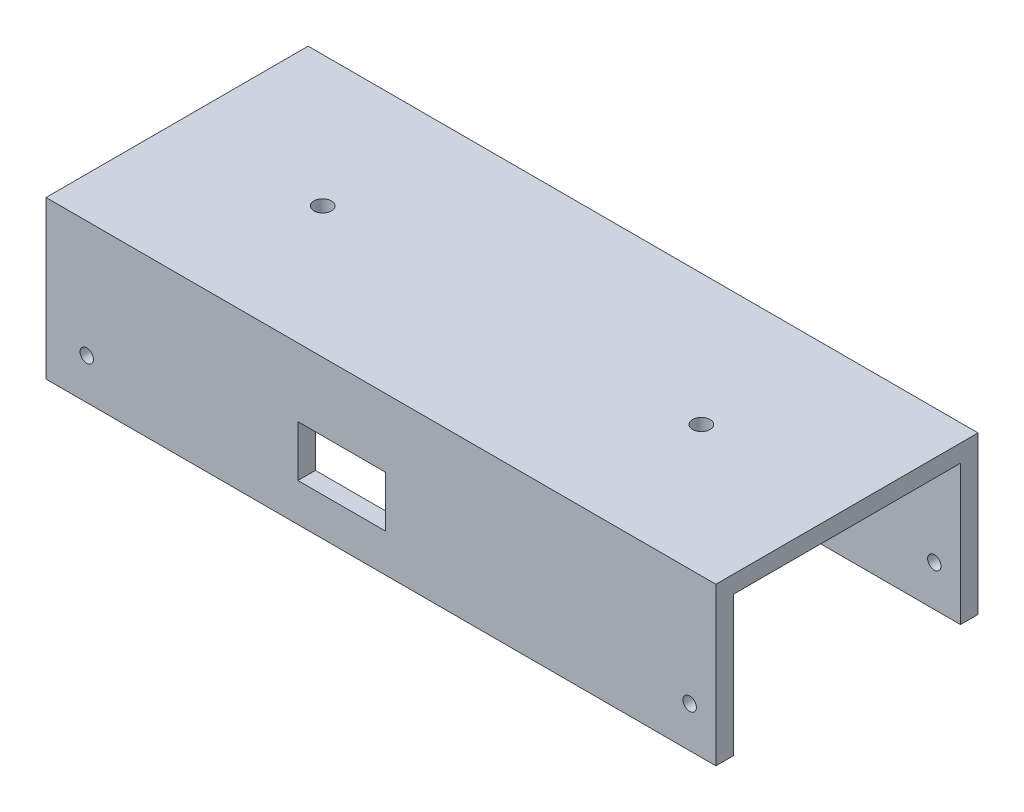
SolidWorks part; units mm, degrees
ref_plane "Front Plane" through (0, 0, 0) normal (0, 0, 1) x (1, 0, 0)
ref_plane "Top Plane" through (0, 0, 0) normal (0, 1, 0) x (1, 0, 0)
ref_plane "Right Plane" through (0, 0, 0) normal (1, 0, 0) x (0, 0, -1)
sketch "Sketch1" plane through (0, 0, 0) normal (0, 0, 1) x (1, 0, 0)
  line L9 (21.172, -17.9478) -> (91.172, -17.9478)
  line L10 (21.172, -17.9478) -> (21.172, -40.3878)
  line L11 (4.5, -8) -> (200.727, -8) construction
  line L12 (4.5, -8) -> (-67.0185, -8) construction
  line L13 (21.172, -40.3878) -> (91.172, -40.3878)
  line L14 (91.172, -17.9478) -> (91.172, -40.3878)
  line L15 (0, 0) -> (115, 0)
  line L16 (0, 0) -> (0, 27)
  line L17 (0, 27) -> (115, 27)
  line L18 (115, 0) -> (115, 27)
  circle A0 centre (4.5, 7) radius 1.15
  circle A1 centre (4.5, 7) radius 15 construction
  circle A3 centre (77.172, -29.1678) radius 3.6067
  circle A4 centre (110.5, 7) radius 15 construction
  circle A5 centre (110.5, 7) radius 1.15
  point P19 (21.172, -29.1678)
  dimension "D4" = 30
  dimension "D2" = 14
  dimension "D7" = 30
  dimension "D11" = 4.5
  dimension "D13" = 2.3
  dimension "D14" = 2.3
  dimension "D3" = 70
  dimension "D5" = 22.44
  dimension "D6" = 115
  dimension "D8" = 27
  dimension "D9" = 4.5
  dimension "D10" = 7
  dimension "D12" = 7
extrude "Boss-Extrude5" add sketch "Sketch1" along normal blind 45 contours L16 L15 L18 L17
shell "Shell9" thickness 3 removed face at (115, 13.5, 22.5) removed face at (57.5, 0, 22.5) removed face at (0, 13.5, 22.5)
sketch "Sketch3" plane through (0, 0, 0) normal (0, 0, -1) x (-1, 0, 0)
  line L0 (0, 0) -> (-115, 0) construction
  line L1 (-115, 0) -> (-115, 27) construction
  line L2 (0, 0) -> (0, 27) construction
  circle A0 centre (-7, 7) radius 1.15
  circle A1 centre (-110.5, 7) radius 1.15
  dimension "D1" = 2.3
  dimension "D2" = 2.3
  dimension "D3" = 7
  dimension "D4" = 4.5
  dimension "D5" = 7
  dimension "D6" = 7
extrude "Cut-Extrude2" cut sketch "Sketch3" against normal blind 79
sketch "Sketch6" plane through (0, 0, 0) normal (0, 0, -1) x (-1, 0, 0)
  line L0 (-71.9735, 19.9938) -> (-46.8835, 19.9938) construction
  line L1 (-71.9735, 21.7438) -> (-46.8835, 21.7438)
  line L2 (-71.9735, 18.2438) -> (-46.8835, 18.2438)
  line L7 (41.5249, -18.7743) -> (41.5249, -41.2143) construction
  line L8 (-89.8735, 11.4938) -> (-14.8735, 11.4938) construction
  line L9 (-89.8735, 15.9938) -> (-14.8735, 15.9938)
  line L10 (-89.8735, 6.9938) -> (-14.8735, 6.9938)
  line L11 (-14.8735, 11.4938) -> (-17.326, 11.4938) construction
  line L12 (-71.9735, 2.9938) -> (-46.8835, 2.9938) construction
  line L13 (-71.9735, 1.2438) -> (-46.8835, 1.2438)
  line L14 (-71.9735, 4.7438) -> (-46.8835, 4.7438)
  line L15 (4.7849, -29.9943) -> (74.7849, -29.9943) construction
  line L20 (4.7849, -18.7743) -> (74.7849, -18.7743)
  line L21 (4.7849, -18.7743) -> (4.7849, -41.2143)
  line L22 (4.7849, -41.2143) -> (74.7849, -41.2143)
  line L23 (74.7849, -18.7743) -> (74.7849, -41.2143)
  line L24 (-115, 0) -> (-115, 27) construction
  line L25 (63.3749, -18.7743) -> (63.3749, -41.2143) construction
  line L26 (0, 27) -> (-115, 27) construction
  arc A4 (-89.8735, 15.9938) -> (-89.8735, 6.9938) centre (-89.8735, 11.4938) ccw
  arc A5 (-71.9735, 21.7438) -> (-71.9735, 18.2438) centre (-71.9735, 19.9938) ccw
  arc A6 (-46.8835, 18.2438) -> (-46.8835, 21.7438) centre (-46.8835, 19.9938) ccw
  arc A7 (-14.8735, 6.9938) -> (-14.8735, 15.9938) centre (-14.8735, 11.4938) ccw
  arc A8 (-71.9735, 1.2438) -> (-71.9735, 4.7438) centre (-71.9735, 2.9938) cw
  arc A9 (-46.8835, 4.7438) -> (-46.8835, 1.2438) centre (-46.8835, 2.9938) cw
  circle A15 centre (16.1349, -29.9943) radius 1.5
  circle A16 centre (36.3249, -21.4943) radius 1.5
  circle A17 centre (36.3249, -38.4943) radius 1.5
  circle A18 centre (36.3249, -38.4943) radius 1.5
  circle A19 centre (27.0349, -29.9943) radius 2.3201
  point P11 (-59.4285, 19.9938)
  point P19 (-52.3735, 11.4938)
  point P31 (-59.4285, 2.9938)
  dimension "D8" = 1.75
  dimension "D13" = 4.5
  dimension "D10" = 3
  dimension "D14" = 3
  dimension "D9" = 25.09
  dimension "D2" = 8.5
  dimension "D3" = 17.9
  dimension "D4" = 70
  dimension "D5" = 22.44
  dimension "D6" = 36.74
  dimension "D7" = 11.35
  dimension "D11" = 5.2
  dimension "D12" = 8.5
  dimension "D15" = 22.25
  dimension "D16" = 75
  dimension "D17" = 25.1265
  dimension "D18" = 11.41
  dimension "D19" = 15.5062
extrude "Cut-Extrude8" cut sketch "Sketch6" against normal blind 23 contours L10 A7 L9 | L2 A6 L1 A5 | L13 A9 L14 A8 region at (59.4285, 19.9938, 0) region at (52.3735, 11.4938, 0)
sketch "Sketch7" plane through (0, 0, 45) normal (0, 0, 1) x (1, 0, 0)
  line L1 (43.2462, 15.2962) -> (58.2462, 15.2962)
  line L2 (43.2462, 15.2962) -> (43.2462, 6.5462)
  line L3 (43.2462, 6.5462) -> (58.2462, 6.5462)
  line L4 (58.2462, 15.2962) -> (58.2462, 6.5462)
  line L5 (0, 0) -> (115, 0) construction
  line L7 (0, 0) -> (0, 27) construction
  point P4 (0, 0)
  point P5 (51.854, 15.2962)
  point P6 (43.2462, 15.2962)
  dimension "D1" = 43.2462
  dimension "D2" = 15
  dimension "D3" = 8.75
  dimension "D4" = 15.2962
extrude "Cut-Extrude9" cut sketch "Sketch7" against normal blind 20
sketch "Sketch9" plane through (0, 24, 0) normal (0, -1, 0) x (1, 0, 0)
  line L0 (0, 20.1086) -> (115, 20.1086) construction
  line L1 (0, 42) -> (0, 3) construction
  line L2 (115, 42) -> (115, 3) construction
  text T0 "group 3"
extrude "Cut-Extrude10" cut sketch "Sketch9" against normal blind 1
sketch "Sketch10" plane through (0, 24, 0) normal (0, -1, 0) x (1, 0, 0)
  line L0 (0, 42) -> (0, 3) construction
  line L1 (115, 42) -> (115, 3) construction
  circle A0 centre (25, 22.5) radius 1.5
  circle A1 centre (90, 22.5) radius 1.5
  point P8 (115, 22.5)
  dimension "D3" = 3
  dimension "D4" = 3
  dimension "D1" = 25
  dimension "D2" = 25
extrude "Cut-Extrude11" cut sketch "Sketch10" against normal blind 26
equation "\"slot­_width\"=25.09"
equation "\"D9@Sketch6\"=\"slot­_width\""
